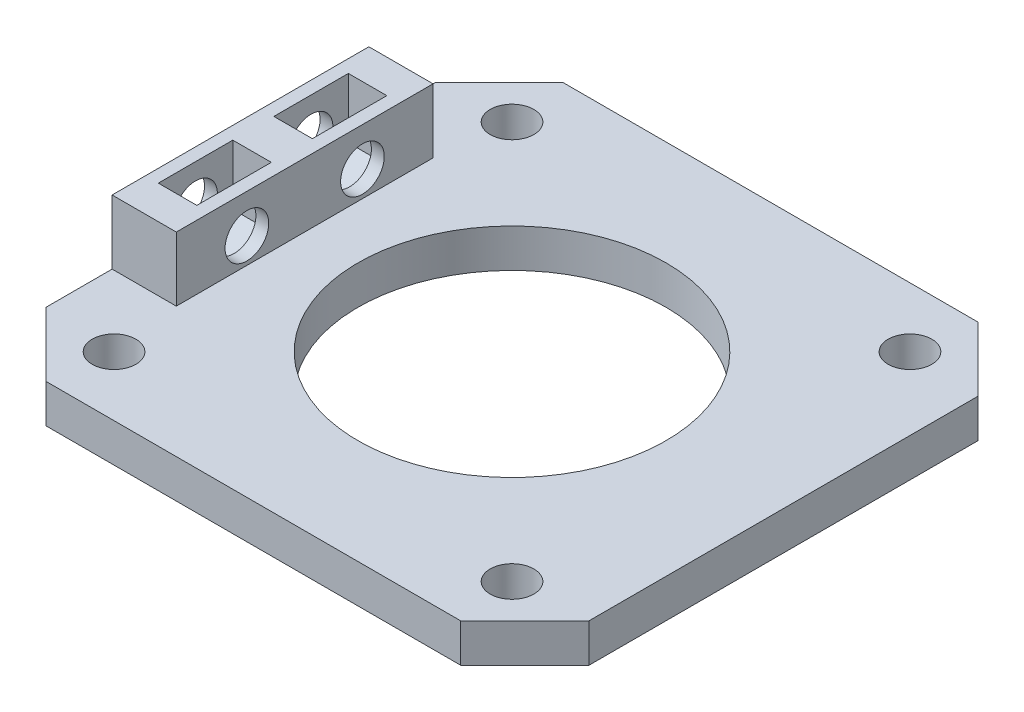
SolidWorks part; units mm, degrees
ref_plane "Alzado" through (0, 0, 0) normal (0, 0, 1) x (1, 0, 0)
ref_plane "Planta" through (0, 0, 0) normal (0, 1, 0) x (1, 0, 0)
ref_plane "Vista lateral" through (0, 0, 0) normal (1, 0, 0) x (0, 0, -1)
sketch "Croquis1" plane through (0, 0, 0) normal (0, 1, 0) x (1, 0, 0)
  line L1 (21.15, -20.15) -> (-21.15, -20.15)
  line L2 (21.15, -20.15) -> (21.15, 20.15)
  line L3 (21.15, 20.15) -> (-21.15, 20.15)
  line L4 (-21.15, -20.15) -> (-21.15, 20.15)
  line L7 (15.5, -15.5) -> (-15.5, -15.5) construction
  line L8 (15.5, -15.5) -> (15.5, 15.5) construction
  line L9 (15.5, 15.5) -> (-15.5, 15.5) construction
  line L10 (-15.5, -15.5) -> (-15.5, 15.5) construction
  line L11 (15.5, -15.5) -> (-15.5, 15.5) construction
  line L12 (15.5, 15.5) -> (-15.5, -15.5) construction
  circle A0 centre (0, 0) radius 12
  circle A1 centre (-15.5, 15.5) radius 1.7
  circle A2 centre (15.5, 15.5) radius 1.7
  circle A3 centre (-15.5, -15.5) radius 1.7
  circle A4 centre (15.5, -15.5) radius 1.7
  point P0 (0, 0)
  point P6 (0, 0)
  point P17 (-21.15, 0)
  point P18 (0, 20.15)
  dimension "D4" = 3.4
  dimension "D5" = 24
  dimension "D1" = 40.3
  dimension "D2" = 42.3
  dimension "D3" = 31
  dimension "D6" = 31
extrude "Saliente-Extruir1" add sketch "Croquis1" along normal blind 3
fillet "Chaflán2" radius 5 1 edges at (21.15, 1.5, -20.15) type face fillet profile chamfer first side face at (0, 1.5, -20.15) second side face at (21.15, 1.5, 0)
fillet "Chaflán3" radius 5 1 edges at (21.15, 1.5, 20.15) type face fillet profile chamfer first side face at (0, 1.5, 20.15) second side face at (21.15, 1.5, 2.5)
fillet "Chaflán4" radius 5 1 edges at (-21.15, 1.5, 20.15) type face fillet profile chamfer first side face at (-21.15, 1.5, 0) second side face at (-2.5, 1.5, 20.15)
fillet "Chaflán5" radius 5 1 edges at (-21.15, 1.5, -20.15) type face fillet profile chamfer first side face at (-21.15, 1.5, -2.5) second side face at (-2.5, 1.5, -20.15)
sketch "Croquis2" plane through (0, 3, 0) normal (0, 1, 0) x (1, 0, 0)
  line L0 (-21.15, 15.15) -> (-21.15, -15.15) construction
  line L1 (-16.15, -10) -> (-21.15, -10)
  line L2 (-16.15, -10) -> (-16.15, 10)
  line L3 (-16.15, 10) -> (-21.15, 10)
  line L4 (-21.15, -10) -> (-21.15, 10)
  line L5 (-16.15, -10) -> (-21.15, 10) construction
  line L6 (-16.15, 10) -> (-21.15, -10) construction
  point P0 (-18.65, 0)
  dimension "D1" = 5
  dimension "D2" = 20
extrude "Saliente-Extruir2" add sketch "Croquis2" along normal blind 5
sketch "Croquis3" plane through (-21.15, 0, 0) normal (-1, 0, 0) x (0, 0, 1)
  line L0 (-4.5, 5) -> (4.5, 5) construction
  circle A0 centre (-4.5, 5) radius 1.7
  circle A1 centre (4.5, 5) radius 1.7
  point P2 (0, 5)
  dimension "D1" = 3.4
  dimension "D2" = 9
  dimension "D3" = 5
extrude "Cortar-Extruir1" cut sketch "Croquis3" against normal blind 7
ref_plane "Plano1" through (-18.65, 0, 0) normal (1, 0, 0) x (0, 0, -1)
sketch "Croquis4" plane through (-18.65, 0, 0) normal (1, 0, 0) x (0, 0, -1)
  line L0 (-7.4012, 6.675) -> (-7.4012, 13.325)
  line L1 (-4.5, 8.35) -> (-7.4012, 6.675) construction
  line L2 (-7.4012, 6.675) -> (-7.4012, 3.325)
  line L3 (-7.4012, 3.325) -> (-4.5, 1.65)
  line L4 (-4.5, 1.65) -> (-1.5988, 3.325)
  line L5 (-1.5988, 3.325) -> (-1.5988, 6.675)
  line L6 (-1.5988, 6.675) -> (-4.5, 8.35) construction
  line L7 (4.5, 8.35) -> (1.5988, 6.675) construction
  line L8 (1.5988, 6.675) -> (1.5988, 3.325)
  line L9 (1.5988, 3.325) -> (4.5, 1.65)
  line L10 (4.5, 1.65) -> (7.4012, 3.325)
  line L11 (7.4012, 3.325) -> (7.4012, 6.675)
  line L12 (7.4012, 6.675) -> (4.5, 8.35) construction
  line L13 (-7.4012, 13.325) -> (-1.5988, 13.325)
  line L14 (-1.5988, 13.325) -> (-1.5988, 6.675)
  line L15 (1.5988, 6.675) -> (1.5988, 13.325)
  line L16 (1.5988, 13.325) -> (7.4012, 13.325)
  line L17 (7.4012, 13.325) -> (7.4012, 6.675)
  line L18 (-10, 8) -> (-10, 3) construction
  circle A0 centre (-4.5, 5) radius 3.35 construction
  circle A1 centre (4.5, 5) radius 3.35 construction
  dimension "D1" = 6.7
  dimension "D2" = 10
extrude "Cortar-Extruir2" cut sketch "Croquis4" against normal blind 1.5 and the other way blind 1.5
